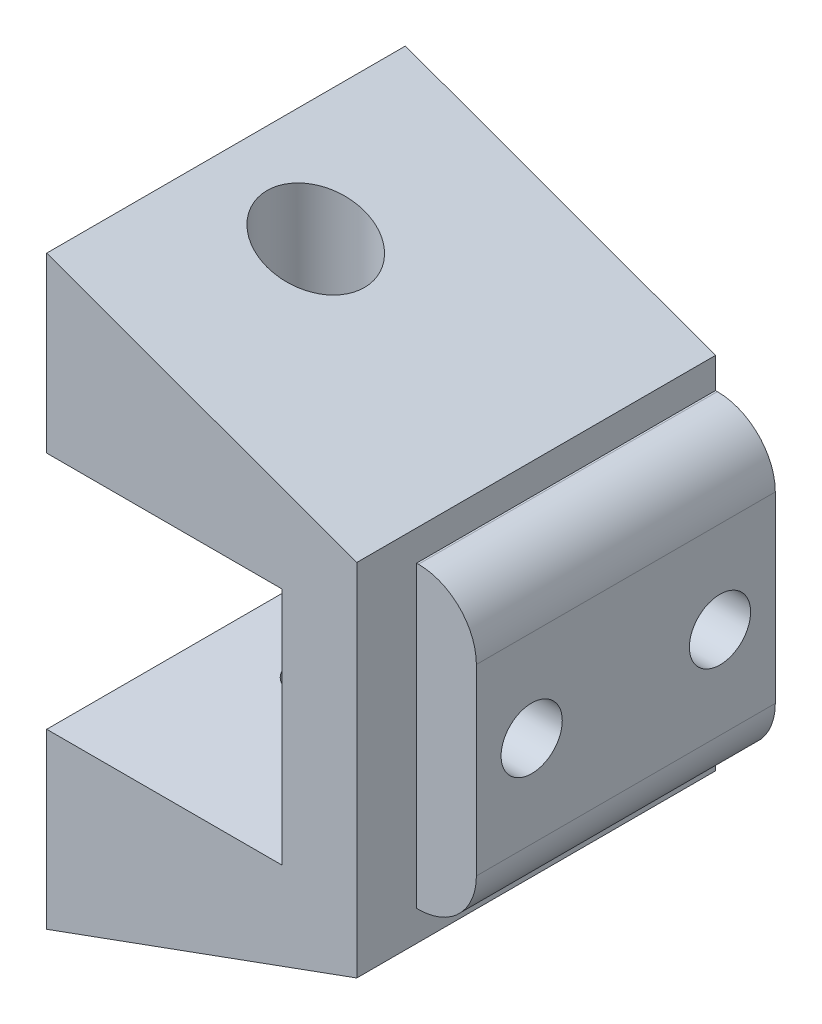
SolidWorks part; units mm, degrees
material "ABS"
ref_plane "Front Plane" through (0, 0, 0) normal (1, 0, 0) x (0, 1, 0)
ref_plane "Top Plane" through (0, 0, 0) normal (0, 0, 1) x (0, 1, 0)
ref_plane "Right Plane" through (0, 0, 0) normal (0, 1, 0) x (-1, 0, 0)
sketch "Sketch3" plane through (0, 0, 0) normal (1, 0, 0) x (0, 1, 0)
  line L1 (-25.4, 30.48) -> (25.4, 30.48)
  line L2 (-25.4, 30.48) -> (-25.4, 0)
  line L3 (-25.4, 0) -> (25.4, 0)
  line L4 (25.4, 30.48) -> (25.4, 0)
  point P4 (0, 0)
  dimension "D1" = 50.8
  dimension "D2" = 30.48
extrude "Boss-Extrude1" add sketch "Sketch3" along normal blind 6.35
sketch "Sketch4" plane through (0, 0, 0) normal (-1, 0, 0) x (0, -1, 0)
  line L0 (25.4, 0) -> (-25.4, 0) construction
  line L1 (-25.4, 30.48) -> (-10.16, 30.48)
  line L2 (-25.4, 30.48) -> (-25.4, 0)
  line L3 (-25.4, 0) -> (-10.16, 0)
  line L4 (-10.16, 30.48) -> (-10.16, 0)
  line L6 (25.4, 30.48) -> (10.16, 30.48)
  line L7 (25.4, 30.48) -> (25.4, 0)
  line L8 (25.4, 0) -> (10.16, 0)
  line L9 (10.16, 30.48) -> (10.16, 0)
  dimension "D1" = 15.24
  dimension "D2" = 15.24
extrude "Boss-Extrude2" add sketch "Sketch4" along normal blind 20
sketch "Sketch5" plane through (0, 25.4, 0) normal (0, 1, 0) x (-1, 0, 0)
  line L0 (-6.35, 15.24) -> (20, 15.24) construction
  line L1 (-6.35, 0) -> (-6.35, 30.48) construction
  line L2 (20, 30.48) -> (20, 0) construction
  line L3 (6.825, 30.48) -> (6.825, 0) construction
  line L4 (-6.35, 30.48) -> (20, 30.48) construction
  line L5 (-6.35, 0) -> (20, 0) construction
  circle A0 centre (12.38, 15.24) radius 4.135
  dimension "D1" = 8.27
  dimension "D2" = 7.62
extrude "Cut-Extrude1" cut sketch "Sketch5" against normal blind 10.668
sketch "Sketch6" plane through (0, 14.732, 0) normal (0, 1, 0) x (-1, 0, 0)
  line L0 (8.245, 15.24) -> (16.515, 15.24) construction
  circle A0 centre (12.38, 15.24) radius 4.135 construction
  circle A1 centre (12.38, 15.24) radius 4.135 construction
  circle A2 centre (12.38, 15.24) radius 2.35
  dimension "D1" = 4.7
extrude "Cut-Extrude2" cut sketch "Sketch6" against normal blind 8
sketch "Sketch7" plane through (0, -25.4, 0) normal (0, -1, 0) x (1, 0, 0)
  line L0 (-20, 15.24) -> (6.35, 15.24) construction
  line L1 (-20, 0) -> (-20, 30.48) construction
  line L2 (6.35, 30.48) -> (6.35, 0) construction
  line L3 (-6.825, 30.48) -> (-6.825, 0) construction
  line L4 (6.35, 30.48) -> (-20, 30.48) construction
  line L5 (6.35, 0) -> (-20, 0) construction
  circle A0 centre (-12.38, 15.24) radius 4.135
  dimension "D1" = 8.27
  dimension "D2" = 7.62
extrude "Cut-Extrude3" cut sketch "Sketch7" against normal blind 10.668
sketch "Sketch8" plane through (0, -14.732, 0) normal (0, -1, 0) x (1, 0, 0)
  line L0 (-16.515, 15.24) -> (-8.245, 15.24) construction
  line L1 (-12.38, 19.375) -> (-12.38, 11.105) construction
  circle A0 centre (-12.38, 15.24) radius 4.135 construction
  circle A1 centre (-12.38, 15.24) radius 4.135 construction
  circle A2 centre (-12.38, 15.24) radius 2.135
  dimension "D1" = 4.27
extrude "Cut-Extrude4" cut sketch "Sketch8" against normal blind 8
sketch "Sketch10" plane through (6.35, 0, 0) normal (1, 0, 0) x (0, 1, 0)
  line L0 (0, 0) -> (0, 30.48) construction
  line L1 (25.4, 30.48) -> (-25.4, 30.48) construction
  line L2 (-25.4, 0) -> (25.4, 0) construction
  line L3 (-12.7, 0) -> (12.7, 0)
  line L4 (-12.7, 0) -> (-12.7, 25.4)
  line L5 (-12.7, 25.4) -> (12.7, 25.4)
  line L6 (12.7, 0) -> (12.7, 25.4)
  line L7 (-12.7, 12.7) -> (12.7, 12.7) construction
  circle A0 centre (0, 20.701) radius 2.6
  circle A1 centre (0, 4.701) radius 2.6
  point P11 (0, 0)
  point P18 (0, 0)
  point P19 (0, 19.05)
  point P20 (0, 19.05)
  dimension "D3" = 5.2
  dimension "D4" = 5.2
  dimension "D1" = 25.4
  dimension "D2" = 25.4
  dimension "D5" = 16
  dimension "D6" = 4.699
extrude "Boss-Extrude4" add sketch "Sketch10" along normal blind 5.08
chamfer "Chamfer1" distance 27.78 angle 20 2 edges at (6.35, 25.4, 15.24) (6.35, -25.4, 15.24) first distance on face at (-12.38, 25.4, 19.375) first distance on face at (-12.38, -25.4, 11.105)
fillet "Fillet2" radius 4.92 2 edges at (11.43, 12.7, 12.7) (11.43, -12.7, 12.7)
sketch "Sketch12" plane through (6.35, 0, 0) normal (1, 0, 0) x (0, 1, 0)
  line L0 (0, 18.101) -> (0, 23.301) construction
  line L1 (-2.6, 20.701) -> (2.6, 20.701) construction
  circle A0 centre (0, 20.701) radius 2.6 construction
  circle A1 centre (0, 20.701) radius 2.6 construction
  circle A2 centre (0, 20.701) radius 2.6
extrude "Cut-Extrude6" cut sketch "Sketch12" against normal through all
sketch "Sketch13" plane through (6.35, 0, 0) normal (1, 0, 0) x (0, 1, 0)
  line L0 (0, 2.101) -> (0, 7.301) construction
  line L1 (-2.6, 4.701) -> (2.6, 4.701) construction
  circle A0 centre (0, 4.701) radius 2.6 construction
  circle A1 centre (0, 4.701) radius 2.6 construction
  circle A2 centre (0, 4.701) radius 2.6
extrude "Cut-Extrude7" cut sketch "Sketch13" against normal through all
